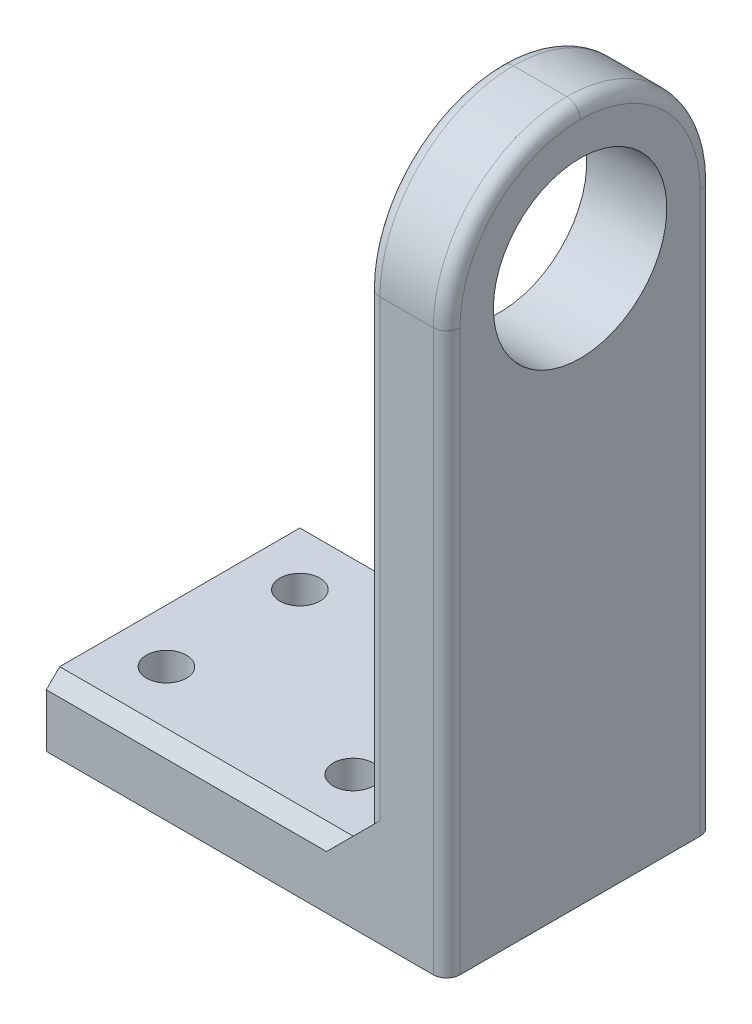
SolidWorks part; units mm, degrees
ref_plane "Front Plane" through (0, 0, 0) normal (0, 0, 1) x (1, 0, 0)
ref_plane "Top Plane" through (0, 0, 0) normal (0, 1, 0) x (1, 0, 0)
ref_plane "Right Plane" through (0, 0, 0) normal (1, 0, 0) x (0, 0, -1)
sketch "Sketch1" plane through (0, 0, 0) normal (0, 1, 0) x (1, 0, 0)
  line L1 (-75, 10) -> (75, 10)
  line L2 (-75, 10) -> (-75, -10)
  line L3 (-75, -10) -> (75, -10)
  line L4 (75, 10) -> (75, -10)
  line L5 (-75, 10) -> (75, -10) construction
  line L6 (-75, -10) -> (75, 10) construction
  point P0 (0, 0)
  dimension "D1" = 150
  dimension "D2" = 20
extrude "Boss-Extrude1" add sketch "Sketch1" along normal blind 5
sketch "Sketch2" plane through (-75, 0, 0) normal (-1, 0, 0) x (0, 0, 1)
  line L0 (-10, 5) -> (-10, 52)
  line L1 (-10, 52) -> (10, 52)
  line L2 (10, 52) -> (10, 5)
  line L3 (10, 5) -> (-10, 5)
  line L4 (0, 52) -> (0, 0) construction
  circle A2 centre (0, 42) radius 6.5
  dimension "D3" = 37
  dimension "D2" = 13
  dimension "D1" = 47
extrude "Boss-Extrude2" add sketch "Sketch2" against normal blind 6
fillet "Fillet1" radius 10 2 edges at (-72, 52, -10) (-72, 52, 10)
mirror "Mirror1" about plane through (0, 0, 0) normal (1, 0, 0) of "Boss-Extrude2", "Fillet1"
chamfer "Chamfer1" distance 2 angle 45 2 edges at (-69, 5, 0) (69, 5, 0)
fillet "Fillet2" radius 1 16 edges at (-69, 24.5, -10) (-69, 24.5, 10) (-69, 49.0711, 7.0711) (-75, 21, 10) (-75, 49.0711, 7.0711) (-75, 49.0711, -7.0711) (75, 21, 10) (75, 49.0711, 7.0711) (75, 49.0711, -7.0711) (69, 24.5, 10) (69, 49.0711, 7.0711) (69, 49.0711, -7.0711) (-69, 49.0711, -7.0711) (-75, 21, -10) (75, 21, -10) (69, 24.5, -10)
chamfer "Chamfer2" distance 1 angle 45 2 edges at (0, 5, 10) (0, 5, -10)
sketch "Sketch3" plane through (-75, 0, 0) normal (-1, 0, 0) x (0, 0, 1)
  line L1 (-17.7124, 0) -> (17.8679, 0)
  line L2 (-17.7124, 0) -> (-17.7124, 66.1178)
  line L3 (-17.7124, 66.1178) -> (17.8679, 66.1178)
  line L4 (17.8679, 0) -> (17.8679, 66.1178)
extrude "Cut-Extrude1" cut sketch "Sketch3" against normal blind 120
sketch "Sketch4" plane through (0, 5, 0) normal (0, 1, 0) x (1, 0, 0)
  line L0 (49, 9) -> (49, -9) construction
  line L1 (67, 9) -> (45, 9) construction
  line L2 (45, -9) -> (67, -9) construction
  line L3 (45, 0) -> (67, 0) construction
  line L4 (56, 9) -> (56, -9) construction
  line L5 (63, 9) -> (63, -9) construction
  line L6 (45, -9) -> (45, 9) construction
  line L7 (67, -9) -> (67, 9) construction
  line L8 (45, -5) -> (67, -5) construction
  line L9 (45, 5) -> (67, 5) construction
  circle A0 centre (49, 5) radius 1.5
  circle A1 centre (49, -5) radius 1.5
  circle A2 centre (63, -5) radius 1.5
  circle A3 centre (63, 5) radius 1.5
  dimension "D5" = 3
  dimension "D1" = 5
  dimension "D2" = 5
  dimension "D3" = 7
  dimension "D4" = 7
extrude "Cut-Extrude2" cut sketch "Sketch4" against normal blind 10
